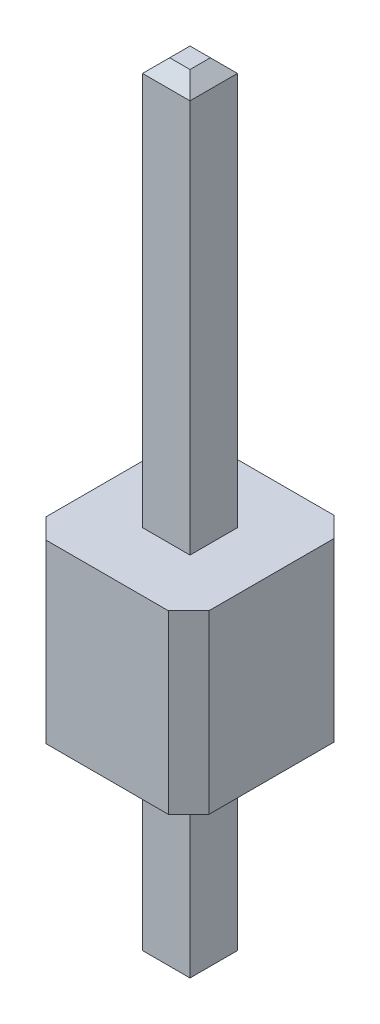
SolidWorks part; units mm, degrees
ref_plane "Спереди" through (0, 0, 0) normal (0, 0, 1) x (1, 0, 0)
ref_plane "Сверху" through (0, 0, 0) normal (0, 1, 0) x (1, 0, 0)
ref_plane "Справа" through (0, 0, 0) normal (1, 0, 0) x (0, 0, -1)
sketch "Эскиз1" plane through (0, 0, 0) normal (0, 1, 0) x (1, 0, 0)
  line L0 (-2.6419, 1.6814) -> (-2.3419, 1.9814)
  line L1 (-2.3419, 1.9814) -> (-0.5419, 1.9814)
  line L2 (-2.6419, 1.6814) -> (-2.6419, -0.1586)
  line L3 (-2.3419, -0.4586) -> (-0.5419, -0.4586)
  line L4 (-0.2419, 1.6814) -> (-0.2419, -0.1586)
  line L5 (-2.6419, 1.9814) -> (-0.2419, -0.4586) construction
  line L6 (-2.6419, -0.4586) -> (-0.2419, 1.9814) construction
  line L7 (-2.6419, -0.1586) -> (-2.3419, -0.4586)
  line L8 (-0.5419, -0.4586) -> (-0.2419, -0.1586)
  line L9 (-0.5419, 1.9814) -> (-0.2419, 1.6814)
  point P0 (-1.4419, 0.7614)
  dimension "D1" = 2.4
  dimension "D2" = 2.44
extrude "Бобышка-Вытянуть1" add sketch "Эскиз1" along normal blind 2.6
sketch "Эскиз2" plane through (0, 2.6, 0) normal (0, 1, 0) x (1, 0, 0)
  line L0 (-2.6419, 0.7614) -> (49997.3581, 0.7614) construction
  line L1 (-2.6419, 1.6814) -> (-2.6419, -0.1586) construction
  line L2 (-1.4419, 1.9814) -> (-1.4419, -49998.0186) construction
  line L3 (-0.5419, 1.9814) -> (-2.3419, 1.9814) construction
  line L5 (-1.7919, 1.1114) -> (-1.0919, 1.1114)
  line L6 (-1.7919, 1.1114) -> (-1.7919, 0.4114)
  line L7 (-1.7919, 0.4114) -> (-1.0919, 0.4114)
  line L8 (-1.0919, 1.1114) -> (-1.0919, 0.4114)
  line L9 (-1.7919, 1.1114) -> (-1.0919, 0.4114) construction
  line L10 (-1.7919, 0.4114) -> (-1.0919, 1.1114) construction
  point P4 (-2.6419, 0.7614)
  point P9 (-1.4419, 1.9814)
  point P10 (-1.4419, 0.7614)
  dimension "D1" = 0.7
  dimension "D2" = 0.7
extrude "Бобышка-Вытянуть2" add sketch "Эскиз2" along normal blind 6
sketch "Эскиз3" plane through (0, 0, 0) normal (0, -1, 0) x (1, 0, 0)
  line L0 (-1.7919, -1.1114) -> (-1.7919, -0.4114) construction
  line L1 (-1.0919, -1.1114) -> (-1.7919, -1.1114) construction
  line L2 (-1.0919, -0.4114) -> (-1.0919, -1.1114) construction
  line L3 (-1.7919, -0.4114) -> (-1.0919, -0.4114) construction
  line L4 (-1.7919, -1.1114) -> (-1.7919, -0.4114)
  line L5 (-1.0919, -1.1114) -> (-1.7919, -1.1114)
  line L6 (-1.0919, -0.4114) -> (-1.0919, -1.1114)
  line L7 (-1.7919, -0.4114) -> (-1.0919, -0.4114)
extrude "Бобышка-Вытянуть3" add sketch "Эскиз3" along normal blind 3
chamfer "Фаска1" distance 0.2 angle 45 8 edges at (-1.7919, -3, -0.7614) (-1.4419, -3, -0.4114) (-1.0919, -3, -0.7614) (-1.4419, -3, -1.1114) (-1.4419, 8.6, -0.4114) (-1.0919, 8.6, -0.7614) (-1.4419, 8.6, -1.1114) (-1.7919, 8.6, -0.7614)
sketch "Эскиз4" plane through (0, -3, 0) normal (0, -1, 0) x (1, 0, 0)
  line L0 (-1.2919, -0.7614) -> (-50001.2919, -0.7614) construction
  line L1 (-1.2919, -0.9114) -> (-1.2919, -0.6114) construction
  line L2 (-1.5919, -0.6114) -> (-1.5919, -0.9114) construction
  line L3 (-1.4419, -0.9114) -> (-1.4419, 49999.0886) construction
  line L4 (-1.5919, -0.9114) -> (-1.2919, -0.9114) construction
  line L5 (-1.2919, -0.6114) -> (-1.5919, -0.6114) construction
  point P4 (-1.2919, -0.7614)
  point P7 (-1.5919, -0.7614)
  point P12 (-1.4419, -0.9114)
  point P15 (-1.4419, -0.6114)
  point P16 (-1.4419, -0.7614)
sketch "Эскиз5" plane through (0, 8.6, 0) normal (0, 1, 0) x (1, 0, 0)
  point P0 (-1.4419, 0.7614)
ref_axis "Ось1" through (-1.4419, 8.6, -0.7614) along (0, -1, 0)
